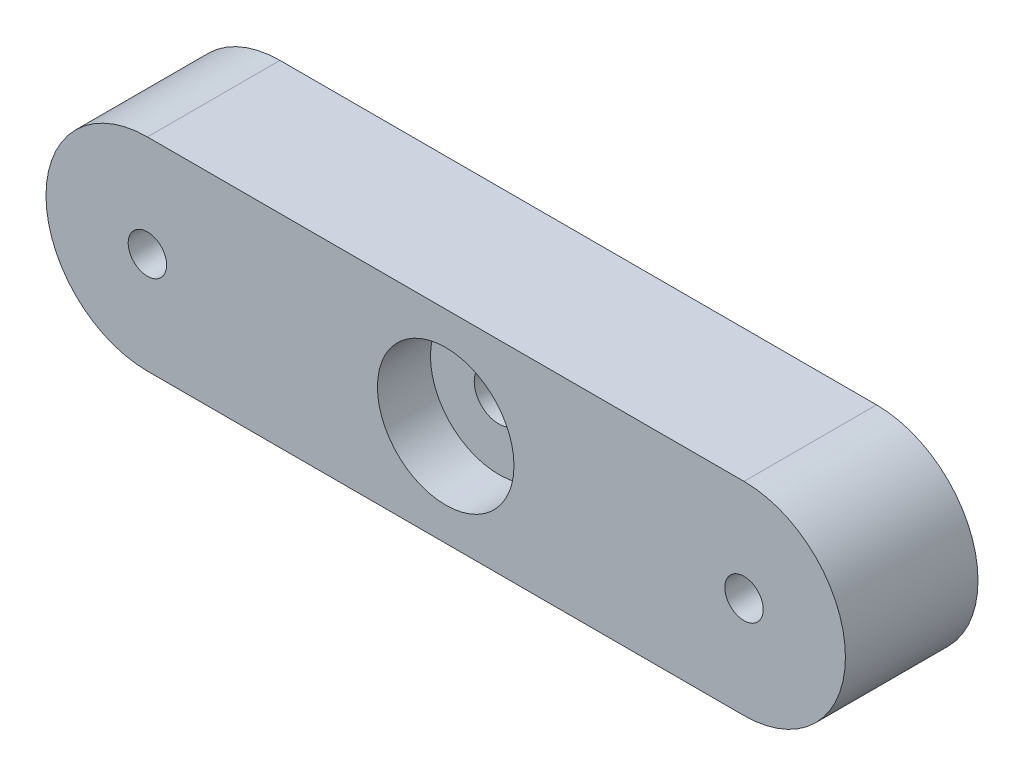
SolidWorks part; units mm, degrees
ref_plane "Спереди" through (0, 0, 0) normal (0, 0, 1) x (1, 0, 0)
ref_plane "Сверху" through (0, 0, 0) normal (0, 1, 0) x (1, 0, 0)
ref_plane "Справа" through (0, 0, 0) normal (1, 0, 0) x (0, 0, -1)
sketch "Эскиз1" plane through (0, 0, 0) normal (0, 0, 1) x (1, 0, 0)
  line L0 (0, 0) -> (45, 0) construction
  line L1 (0, 0) -> (45, 0) construction
  line L2 (0, 7.65) -> (45, 7.65)
  line L3 (0, -7.65) -> (45, -7.65)
  circle A0 centre (0, 0) radius 1.45
  circle A1 centre (45, 0) radius 1.45
  circle A2 centre (22.5, 0) radius 5.15
  arc A3 (0, 7.65) -> (0, -7.65) centre (0, 0) ccw
  arc A4 (45, -7.65) -> (45, 7.65) centre (45, 0) ccw
  point P7 (22.5, 0)
  dimension "D1" = 2.9
  dimension "D2" = 10.3
  dimension "D3" = 45
  dimension "D4" = 15.3
extrude "Бобышка-Вытянуть1" add sketch "Эскиз1" along normal blind 10
sketch "Эскиз2" plane through (0, 0, 0) normal (0, 0, -1) x (-1, 0, 0)
  circle A0 centre (-22.5, 0) radius 5.3054
  circle A1 centre (-22.5, 0) radius 1.85
  dimension "D1" = 3.7
extrude "Бобышка-Вытянуть2" add sketch "Эскиз2" against normal blind 6
